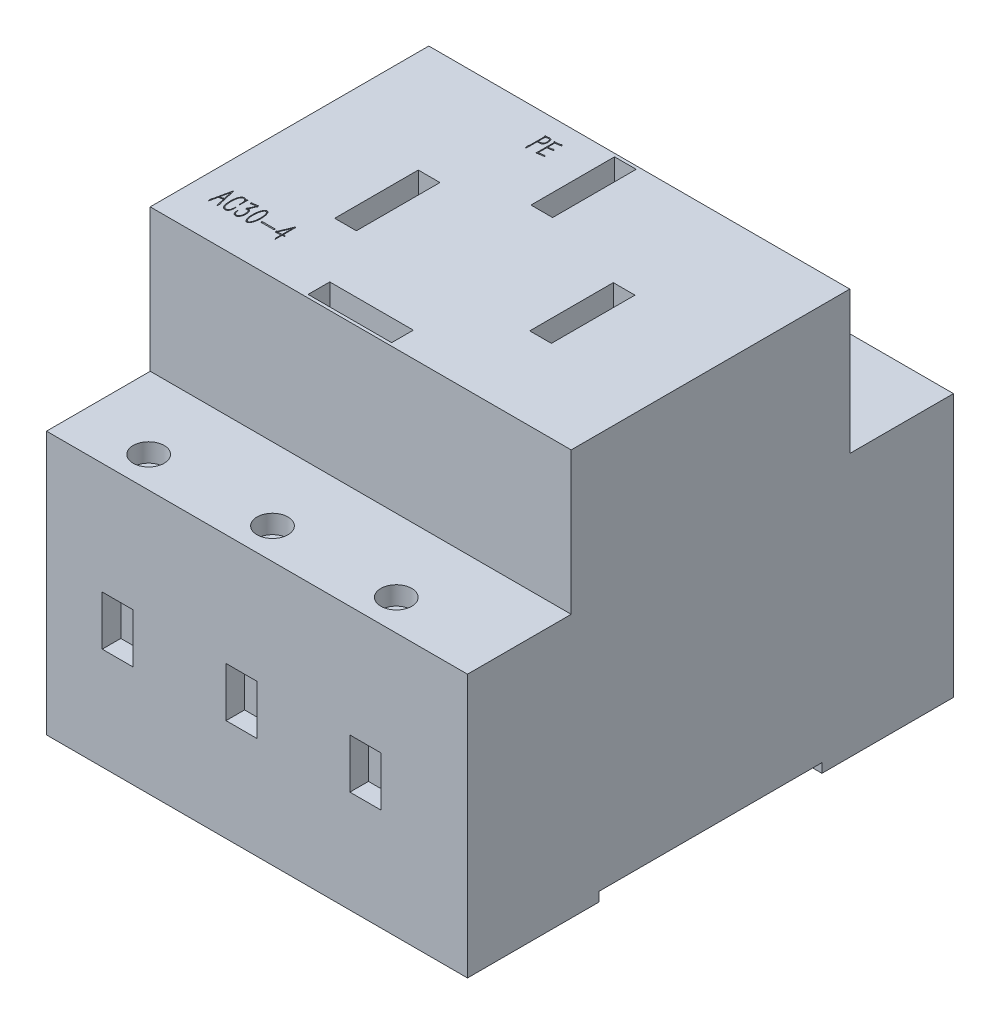
SolidWorks part; units mm, degrees
ref_plane "前视基准面" through (0, 0, 0) normal (0, 0, 1) x (1, 0, 0)
ref_plane "上视基准面" through (0, 0, 0) normal (0, 1, 0) x (1, 0, 0)
ref_plane "右视基准面" through (0, 0, 0) normal (1, 0, 0) x (0, 0, -1)
sketch "草图1" plane through (0, 0, 0) normal (1, 0, 0) x (0, 0, -1)
  line L0 (-22.5, 9.75) -> (-39.25, 9.75)
  line L1 (22.5, 32.75) -> (-22.5, 32.75)
  line L2 (22.5, 32.75) -> (22.5, 9.75)
  line L3 (22.5, -32.75) -> (18, -32.75)
  line L4 (-22.5, 32.75) -> (-22.5, 9.75)
  line L5 (22.5, 32.75) -> (-22.5, -32.75) construction
  line L6 (22.5, -32.75) -> (-22.5, 32.75) construction
  line L7 (39.25, -32.75) -> (18, -32.75)
  line L8 (39.25, -32.75) -> (39.25, 9.75)
  line L9 (39.25, 9.75) -> (22.5, 9.75)
  line L10 (-39.25, -32.75) -> (-39.25, 9.75)
  line L11 (-18, -32.75) -> (-22.5, -32.75)
  line L12 (18, -31.25) -> (-18, -31.25)
  line L13 (18, -31.25) -> (18, -32.75)
  line L14 (-18, -32.75) -> (-39.25, -32.75)
  line L15 (-18, -31.25) -> (-18, -32.75)
  line L16 (22.5, -32.75) -> (39.25, -32.75)
  line L17 (-22.5, -32.75) -> (-39.25, -32.75)
  point P0 (0, 0)
  point P10 (0, -32.75)
  dimension "D1" = 45
  dimension "D2" = 65.5
  dimension "D3" = 42.5
  dimension "D4" = 78.5
  dimension "D5" = 16.75
  dimension "D6" = 36
extrude "凸台-拉伸1" add sketch "草图1" along normal mid plane 68 contours L15 L12 L13 L3 L7 L8 L9 L2 L1 L4 L0 L10 L14 L11 region at (0, -3.3922, 0)
sketch "草图2" plane through (0, 9.75, 0) normal (0, 1, 0) x (1, 0, 0)
  line L0 (34, -39.25) -> (-34, -39.25) construction
  line L1 (-34, -22.5) -> (-34, -39.25) construction
  circle A0 centre (-22.5, -34.25) radius 2.5
  dimension "D1" = 5
  dimension "D3" = 11.5
  dimension "D2" = 5
extrude "切除-拉伸1" cut sketch "草图2" against normal blind 3
sketch "草图3" plane through (0, 0, 39.25) normal (0, 0, 1) x (1, 0, 0)
  line L0 (-34, -32.75) -> (-34, 9.75) construction
  line L1 (-25, -8.25) -> (-20, -8.25)
  line L2 (-25, -8.25) -> (-25, -16.25)
  line L3 (-25, -16.25) -> (-20, -16.25)
  line L4 (-20, -8.25) -> (-20, -16.25)
  line L5 (34, 9.75) -> (-34, 9.75) construction
  dimension "D1" = 5
  dimension "D2" = 8
  dimension "D3" = 9
  dimension "D4" = 18
extrude "切除-拉伸2" cut sketch "草图3" against normal blind 3
pattern_linear "阵列(线性)1" count 3 spacing 20 along (1, 0, 0) of "切除-拉伸2", "切除-拉伸1"
sketch "草图4" plane through (0, 0, 36.25) normal (0, 0, 1) x (1, 0, 0)
  point P0 (-22.5, -12.25)
  point P1 (-2.5, -12.25)
  point P2 (17.5, -12.25)
sketch "草图5" plane through (0, 9.75, 0) normal (0, 1, 0) x (1, 0, 0)
  circle A0 centre (0, 30.875) radius 3
  dimension "D1" = 6
extrude "切除-拉伸3" cut sketch "草图5" against normal blind 3
sketch "草图6" plane through (0, 0, -39.25) normal (0, 0, -1) x (-1, 0, 0)
  line L1 (-2.4489, -8.4358) -> (2.5511, -8.4358)
  line L2 (-2.4489, -8.4358) -> (-2.4489, -16.4358)
  line L3 (-2.4489, -16.4358) -> (2.5511, -16.4358)
  line L4 (2.5511, -8.4358) -> (2.5511, -16.4358)
  line L5 (-2.4489, -8.4358) -> (2.5511, -16.4358) construction
  line L6 (-2.4489, -16.4358) -> (2.5511, -8.4358) construction
  point P0 (0.0511, -12.4358)
  dimension "D1" = 5
  dimension "D2" = 8
extrude "切除-拉伸4" cut sketch "草图6" against normal blind 3
sketch "1_0_Point" plane through (0, 0, -36.25) normal (0, 0, -1) x (-1, 0, 0)
  point P0 (-1.1692, -12.5077)
sketch "草图8" plane through (0, 32.75, 0) normal (0, 1, 0) x (1, 0, 0)
  line L0 (-34, 22.5) -> (-34, -22.5) construction
  line L1 (-17.5, 4.3) -> (-14, 4.3)
  line L2 (-17.5, 4.3) -> (-17.5, -9.2)
  line L3 (-17.5, -9.2) -> (-14, -9.2)
  line L4 (-14, 4.3) -> (-14, -9.2)
  line L5 (14, 4.3) -> (17.5, 4.3)
  line L6 (14, 4.3) -> (14, -9.2)
  line L7 (14, -9.2) -> (17.5, -9.2)
  line L8 (17.5, 4.3) -> (17.5, -9.2)
  line L9 (-3.5, 22) -> (0, 22)
  line L10 (-3.5, 22) -> (-3.5, 8.5)
  line L11 (-3.5, 8.5) -> (0, 8.5)
  line L12 (0, 22) -> (0, 8.5)
  line L13 (-9, -22) -> (4.5, -22)
  line L14 (-9, -22) -> (-9, -18.5)
  line L15 (-9, -18.5) -> (4.5, -18.5)
  line L16 (4.5, -22) -> (4.5, -18.5)
  line L17 (34, 22.5) -> (-34, 22.5) construction
  line L18 (34, 22.5) -> (34, -22.5) construction
  line L19 (34, -22.5) -> (-34, -22.5) construction
  dimension "D1" = 16.5
  dimension "D2" = 3.5
  dimension "D3" = 13.5
  dimension "D4" = 18.2
  dimension "D5" = 13.5
  dimension "D6" = 16.5
  dimension "D7" = 3.5
  dimension "D8" = 18.2
  dimension "D9" = 0.5
  dimension "D10" = 34
  dimension "D11" = 3.5
  dimension "D12" = 13.5
  dimension "D13" = 13.5
  dimension "D14" = 29.5
  dimension "D15" = 3.5
  dimension "D16" = 0.5
extrude "切除-拉伸5" cut sketch "草图8" against normal blind 5
sketch "草图9" plane through (0, 32.75, 0) normal (0, 1, 0) x (1, 0, 0)
  text T0 "\r\n            PE\r\n\r\n\r\n\r\n\r\n  AC30-4"
extrude "切除-拉伸6" cut sketch "草图9" against normal blind 0.3
sketch "草图10" plane through (0, 27.75, 0) normal (0, 1, 0) x (1, 0, 0)
  point P0 (-15.75, -2.45)
  point P1 (15.75, -2.45)
  point P2 (-1.75, 15.25)
  point P3 (-3.5, -20.25)
sketch "0_0_Point" plane through (0, 0, 36.25) normal (0, 0, 1) x (1, 0, 0)
  point P0 (-22.5, -12.25)
other "0_0" parameters "直径"=2, "端头长度"=2
ref_axis "基准轴1" through (-22.5, -12.25, 46.25) along (0, 0, -1)
sketch "0_1_Point" plane through (0, 0, 36.25) normal (0, 0, 1) x (1, 0, 0)
  point P0 (-2.5, -12.25)
other "0_1" parameters "直径"=2, "端头长度"=2
ref_axis "基准轴2" through (-2.5, -12.25, 46.25) along (0, 0, -1)
sketch "0_2_Point" plane through (0, 0, 36.25) normal (0, 0, 1) x (1, 0, 0)
  point P0 (17.5, -12.25)
other "0_2" parameters "直径"=2, "端头长度"=2
ref_axis "基准轴3" through (17.5, -12.25, 46.25) along (0, 0, -1)
other "1_0" parameters "直径"=2, "端头长度"=2
ref_axis "基准轴4" through (1.1692, -12.5077, -46.25) along (0, 0, 1)
